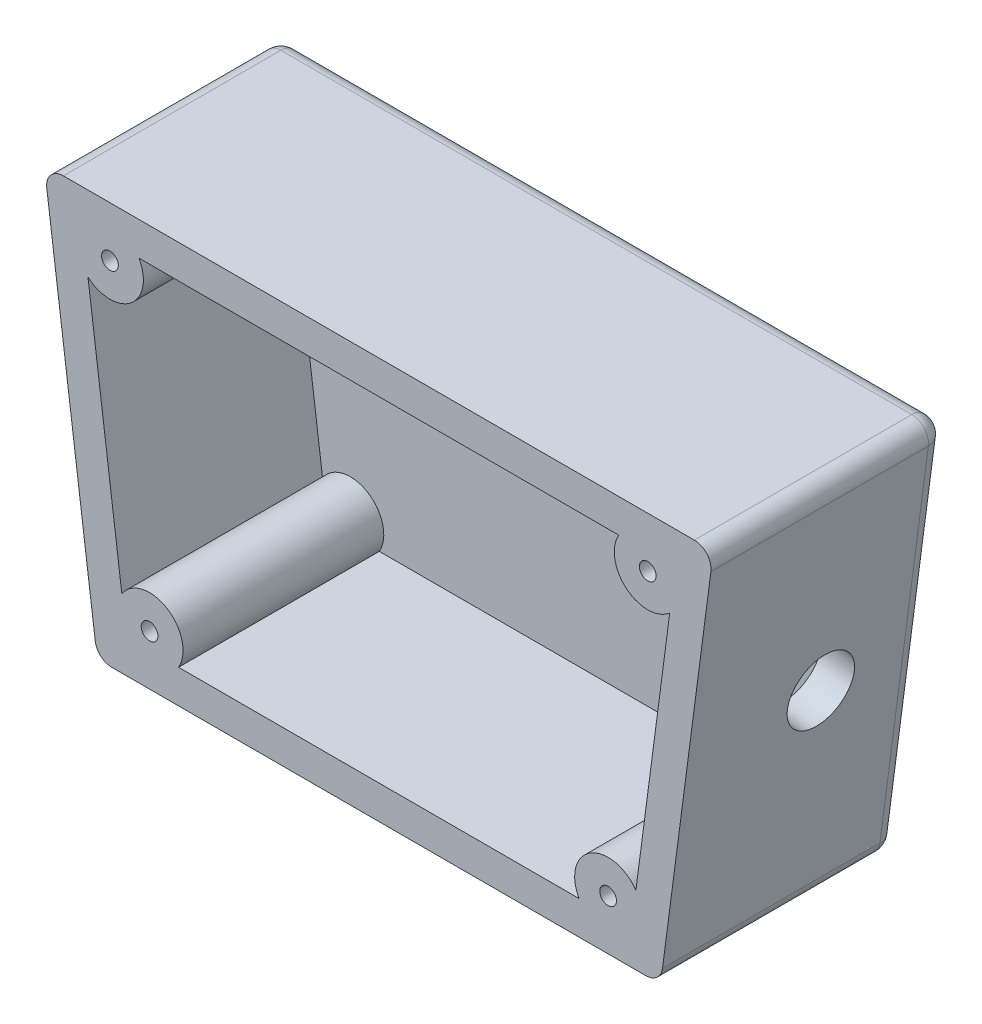
SolidWorks part; units mm, degrees
material "Nylon 101"
ref_plane "Front Plane" through (0, 0, 0) normal (0, 0, 1) x (1, 0, 0)
ref_plane "Top Plane" through (0, 0, 0) normal (0, 1, 0) x (1, 0, 0)
ref_plane "Right Plane" through (0, 0, 0) normal (1, 0, 0) x (0, 0, -1)
sketch "Sketch1" plane through (0, 0, 0) normal (0, 0, 1) x (1, 0, 0)
  line L1 (-53.4681, -38.1) -> (53.4681, -38.1)
  line L2 (-53.4681, -38.1) -> (-63.5, 38.1)
  line L3 (-63.5, 38.1) -> (63.5, 38.1)
  line L4 (53.4681, -38.1) -> (63.5, 38.1)
  line L5 (0, 38.1) -> (0, -38.1) construction
  line L6 (-58.484, 0) -> (58.484, 0) construction
  line L7 (-47.8993, -31.75) -> (47.8993, -31.75)
  line L8 (-47.8993, -31.75) -> (-56.2592, 31.75)
  line L9 (-56.2592, 31.75) -> (56.2592, 31.75)
  line L10 (47.8993, -31.75) -> (56.2592, 31.75)
  line L11 (0, 31.75) -> (0, -31.75) construction
  line L12 (-52.0792, 0) -> (52.0792, 0) construction
  point P0 (0, 0)
  point P4 (0, 0)
  dimension "D1" = 127
  dimension "D2" = 76.2
  dimension "D3" = 6.35
  dimension "D4" = 6.35
  dimension "D5" = 15
extrude "Boss-Extrude1" add sketch "Sketch1" along normal blind 3.175 contours L7 L10 L9 L8 | L1 L4 L3 L2 L10 L7 L8 L9 region at (-57.0156, 0.1933, 0) region at (0, 0.8494, 0)
extrude "Boss-Extrude2" add sketch "Sketch1<3>" against normal blind 3.175 contours L7 L10 L9 L8 region at (0, 0.8494, 0)
sketch "Sketch1<3>" plane through (0, 0, 0) normal (0, 0, 1) x (1, 0, 0) same geometry as "Sketch1"
sketch "Sketch2" plane through (0, 0, 0) normal (0, 0, 1) x (1, 0, 0)
  line L0 (-38.1, 28.8378) -> (0, 0) construction
  line L2 (0, 0) -> (38.1, 28.8378) construction
  line L4 (-33.3375, 22.225) -> (-23.8125, 22.225) construction
  line L5 (-39.6656, 28.575) -> (39.6656, 28.575) construction
  line L6 (-39.6656, 28.575) -> (-39.6656, 15.875)
  line L7 (-39.6656, 15.875) -> (39.6656, 15.875)
  line L8 (39.6656, 28.575) -> (39.6656, 15.875)
  line L9 (0, 22.225) -> (0, 0) construction
  line L10 (-33.3375, 22.225) -> (33.3375, 22.225) construction
  line L11 (-63.5, 38.1) -> (63.5, 38.1) construction
  arc A5 (-38.1, 28.8378) -> (38.1, 28.8378) centre (0, -198.1747) cw construction
  arc A6 (-37.8372, 27.2722) -> (37.8372, 27.2722) centre (0, -198.1747) cw
  arc A7 (-38.3628, 30.4034) -> (38.3628, 30.4034) centre (0, -198.1747) cw
  arc A8 (-37.8372, 27.2722) -> (-38.3628, 30.4034) centre (-38.1, 28.8378) cw
  arc A9 (37.8372, 27.2722) -> (38.3628, 30.4034) centre (38.1, 28.8378) ccw
  circle A10 centre (-33.3375, 22.225) radius 3.175
  circle A11 centre (-23.8125, 22.225) radius 3.175
  circle A12 centre (-14.2875, 22.225) radius 3.175
  circle A13 centre (-4.7625, 22.225) radius 3.175
  circle A14 centre (4.7625, 22.225) radius 3.175
  circle A15 centre (14.2875, 22.225) radius 3.175
  circle A16 centre (23.8125, 22.225) radius 3.175
  circle A17 centre (33.3375, 22.225) radius 3.175
  point P7 (0, 22.225)
  point P8 (39.6656, 22.225)
  point P9 (0, 32.0128)
  dimension "D1" = 15.875
  dimension "D3" = 3.175
  dimension "D4" = 1.5875
  dimension "D7" = 6.35
  dimension "D8" = 8
  dimension "D5" = 1.5875
  dimension "D2" = 76.2
  dimension "D6" = 12.7
  dimension "D9" = 9.525
extrude "Boss-Extrude3" add sketch "Sketch2" along normal blind 6.35 contours A9 A6 A8 L6 L7 L8 A17 A16 A15 A14 A13 A12 A11 A10 | A10 | A11 | A12 | A13 | A14 | A15 | A16 | A17 | A6 A9 A7 A8 region at (0, 22.7442, 0) region at (0, 30.8867, 0) region at (-33.3375, 22.225, 0) region at (-23.8125, 22.225, 0) region at (-14.2875, 22.225, 0) region at (-4.7625, 22.225, 0) region at (4.7625, 22.225, 0) region at (14.2875, 22.225, 0) region at (23.8125, 22.225, 0) region at (33.3375, 22.225, 0)
extrude "Boss-Extrude4" add sketch "Sketch2<3>" along normal blind 12.7 contours A6 A9 A7 A8 region at (0, 30.8867, 0)
sketch "Sketch2<3>" plane through (0, 0, 0) normal (0, 0, 1) x (1, 0, 0) same geometry as "Sketch2"
extrude "Cut-Extrude1" cut sketch "Sketch2<4>" against normal through all both and the other way through all contours A10 | A11 | A12 | A13 | A14 | A15 | A16 | A17 region at (-33.3375, 22.225, 0) region at (-23.8125, 22.225, 0) region at (-14.2875, 22.225, 0) region at (-4.7625, 22.225, 0) region at (4.7625, 22.225, 0) region at (14.2875, 22.225, 0) region at (23.8125, 22.225, 0) region at (33.3375, 22.225, 0)
sketch "Sketch2<4>" plane through (0, 0, 0) normal (0, 0, 1) x (1, 0, 0) same geometry as "Sketch2"
fillet "Fillet1" radius 6.35 2 edges at (39.6656, 15.875, 4.7625) (-39.6656, 15.875, 4.7625)
sketch "Sketch4" plane through (0, 0, 0) normal (0, 0, 1) x (1, 0, 0)
  line L0 (0, 0) -> (0, -19.05) construction
  line L1 (-33.3156, 6.35) -> (33.3156, 6.35) construction
  line L2 (-33.3156, 6.35) -> (-33.3156, -19.05) construction
  line L3 (-33.3156, -19.05) -> (33.3156, -19.05) construction
  line L4 (33.3156, 6.35) -> (33.3156, -19.05) construction
  line L5 (-63.5, 38.1) -> (63.5, 38.1) construction
  line L6 (-33.3156, 6.35) -> (-33.3156, -19.05) construction
  line L7 (-26.9656, 6.35) -> (-26.9656, -19.05)
  line L8 (-39.6656, 6.35) -> (-39.6656, -19.05)
  line L9 (33.3156, 6.35) -> (33.3156, -19.05) construction
  line L10 (39.6656, 6.35) -> (39.6656, -19.05)
  line L11 (26.9656, 6.35) -> (26.9656, -19.05)
  line L12 (-39.6656, 22.225) -> (-39.6656, 28.575) construction
  circle A0 centre (-33.3156, 6.35) radius 3.175
  circle A1 centre (-33.3156, -6.35) radius 3.175
  circle A2 centre (-33.3156, -19.05) radius 3.175
  circle A3 centre (33.3156, 6.35) radius 3.175
  circle A4 centre (33.3156, -6.35) radius 3.175
  circle A5 centre (33.3156, -19.05) radius 3.175
  arc A12 (-26.9656, 6.35) -> (-39.6656, 6.35) centre (-33.3156, 6.35) ccw
  arc A13 (-39.6656, -19.05) -> (-26.9656, -19.05) centre (-33.3156, -19.05) ccw
  arc A14 (39.6656, 6.35) -> (26.9656, 6.35) centre (33.3156, 6.35) ccw
  arc A15 (26.9656, -19.05) -> (39.6656, -19.05) centre (33.3156, -19.05) ccw
  point P4 (-33.3156, -6.35)
  point P22 (33.3156, -6.35)
  dimension "D1" = 6.35
  dimension "D5" = 3.175
  dimension "D2" = 12.7
  dimension "D3" = 31.75
extrude "Boss-Extrude5" add sketch "Sketch4" along normal blind 6.35
extrude "Cut-Extrude2" cut sketch "Sketch4<2>" along normal through all both and the other way through all contours A0 | A1 | A2 | A5 | A4 | A3 region at (-33.3156, 6.35, 0) region at (-33.3156, -6.35, 0) region at (-33.3156, -19.05, 0) region at (33.3156, 6.35, 0) region at (33.3156, -6.35, 0) region at (33.3156, -19.05, 0)
sketch "Sketch4<2>" plane through (0, 0, 0) normal (0, 0, 1) x (1, 0, 0) same geometry as "Sketch4"
extrude "Boss-Extrude6" add sketch "Sketch1<4>" against normal blind 38.1 separate body contours L1 L4 L3 L2 L10 L7 L8 L9 region at (-57.0156, 0.1933, 0)
sketch "Sketch1<4>" plane through (0, 0, 0) normal (0, 0, 1) x (1, 0, 0) same geometry as "Sketch1"
extrude "Boss-Extrude7" add sketch "Sketch1<5>" against normal blind 6.35 from surface contours L7 L10 L9 L8 | L1 L4 L3 L2 L10 L7 L8 L9 region at (-57.0156, 0.1933, 0) region at (0, 0.8494, 0) starting at face at (0, 0, -38.1)
sketch "Sketch1<5>" plane through (0, 0, 0) normal (0, 0, 1) x (1, 0, 0) same geometry as "Sketch1"
sketch "Sketch5" plane through (0, 0, 0) normal (0, 0, 1) x (1, 0, 0)
  line L1 (-43.5137, -28.575) -> (43.5137, -28.575) construction
  line L2 (-43.5137, -28.575) -> (-51.0376, 28.575) construction
  line L3 (-51.0376, 28.575) -> (51.0376, 28.575) construction
  line L4 (-47.8993, -31.75) -> (47.8993, -31.75)
  line L5 (47.8993, -31.75) -> (56.2592, 31.75)
  line L6 (56.2592, 31.75) -> (-56.2592, 31.75)
  line L7 (-56.2592, 31.75) -> (-47.8993, -31.75)
  line L8 (-47.8993, -31.75) -> (47.8993, -31.75)
  line L9 (47.8993, -31.75) -> (56.2592, 31.75)
  line L10 (56.2592, 31.75) -> (-56.2592, 31.75)
  line L11 (-56.2592, 31.75) -> (-47.8993, -31.75)
  line L12 (43.5137, -28.575) -> (51.0376, 28.575) construction
  line L13 (0, 28.575) -> (0, -28.575) construction
  line L14 (-47.2757, 0) -> (47.2757, 0) construction
  circle A0 centre (-51.0376, 28.575) radius 1.5875
  circle A1 centre (51.0376, 28.575) radius 1.5875
  circle A2 centre (43.5137, -28.575) radius 1.5875
  circle A3 centre (-43.5137, -28.575) radius 1.5875
  circle A4 centre (-51.0376, 28.575) radius 6.35
  circle A5 centre (-43.5137, -28.575) radius 6.35
  circle A6 centre (43.5137, -28.575) radius 6.35
  circle A7 centre (51.0376, 28.575) radius 6.35
  point P2 (0, 0)
  dimension "D2" = 4.7625
  dimension "D3" = 3.175
  dimension "D4" = 3.175
  dimension "D5" = 3.175
  dimension "D1" = 0
extrude "Boss-Extrude11" add sketch "Sketch5" against normal through all contours L11 A4 L10 A0 | L8 A5 L11 A3 | L9 A6 L8 A2 | L10 A7 L9 A1 region at (-48.1925, -28.3716, 0) region at (40.2325, -23.3147, 0) region at (-55.5866, 27.7891, 0) region at (47.0976, 23.7877, 0)
extrude "Cut-Extrude9" cut sketch "Sketch5<4>" along normal through all both and the other way through all contours A0 | A3 | A2 | A1 region at (-51.0376, 28.575, 0) region at (51.0376, 28.575, 0) region at (43.5137, -28.575, 0) region at (-43.5137, -28.575, 0)
sketch "Sketch5<4>" plane through (0, 0, 0) normal (0, 0, 1) x (1, 0, 0) same geometry as "Sketch5"
sketch "Sketch6" plane through (-2.7734, -465.2965, 0) normal (-0.9914, 0.1305, 0) x (0, 0, -1)
  line L0 (25.4, -469.3116) -> (0, -469.3116) construction
  line L1 (0, -430.8828) -> (0, -507.7403) construction
  line L4 (44.45, -430.8828) -> (44.45, -507.7403) construction
  circle A0 centre (25.4, -469.3116) radius 6.35
  dimension "D1" = 12.7
  dimension "D2" = 19.05
extrude "Cut-Extrude10" cut sketch "Sketch6" along normal up to next (6.35 mm away) and the other way through all contours A0
chamfer "Chamfer1" distance 2.54 angle 45 4 edges at (52.6251, 28.575, 3.175) (45.1012, -28.575, 3.175) (-41.9262, -28.575, 3.175) (-49.4501, 28.575, 3.175)
fillet "Fillet2" radius 3.175 8 edges at (0, -38.1, -44.45) (58.484, 0, -44.45) (0, 38.1, -44.45) (-58.484, 0, -44.45) (53.4681, -38.1, -22.225) (63.5, 38.1, -22.225) (-53.4681, -38.1, -22.225) (-63.5, 38.1, -22.225)
fillet "Fillet3" radius 3.175 4 edges at (-53.4681, -38.1, 1.5875) (-63.5, 38.1, 1.5875) (63.5, 38.1, 1.5875) (53.4681, -38.1, 1.5875)
delete or keep bodies "Body-Delete/Keep 1" type delete bodies bodies 111
